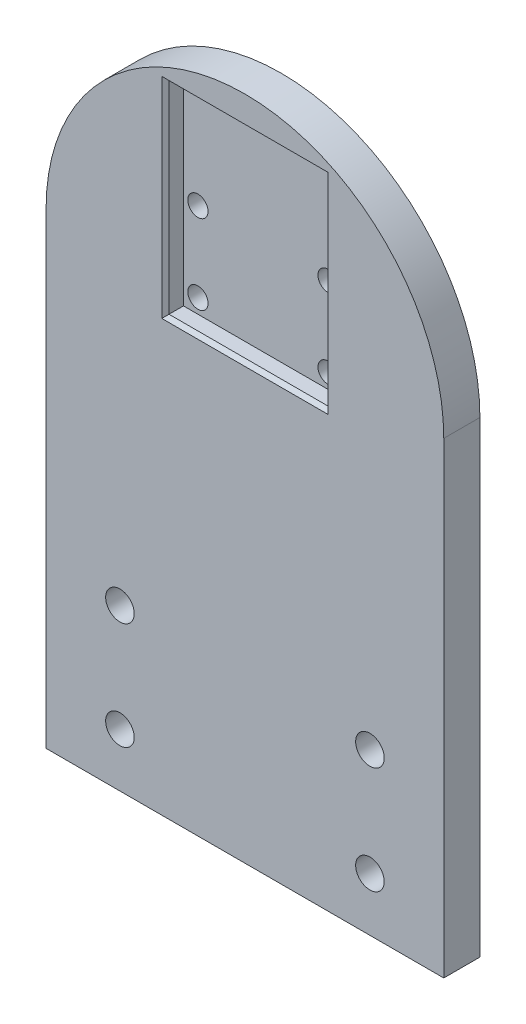
SolidWorks part; units mm, degrees
ref_plane "Front" through (0, 0, 0) normal (0, 0, 1) x (1, 0, 0)
ref_plane "Top" through (0, 0, 0) normal (0, 1, 0) x (1, 0, 0)
ref_plane "Right" through (0, 0, 0) normal (1, 0, 0) x (0, 0, -1)
sketch "草图1" plane through (0, 0, 0) normal (0, 0, 1) x (1, 0, 0)
  line L0 (0, 49.8177) -> (0, 51.7928) construction
  line L1 (-27.5, -14.8177) -> (27.5, -14.8177)
  line L2 (-27.5, -14.8177) -> (-27.5, 14.8177)
  line L3 (-27.5, 14.8177) -> (27.5, 14.8177) construction
  line L4 (27.5, -14.8177) -> (27.5, 14.8177)
  line L5 (-27.5, -14.8177) -> (27.5, 14.8177) construction
  line L6 (-27.5, 14.8177) -> (27.5, -14.8177) construction
  line L7 (-17.2873, -7.4089) -> (17.2873, -7.4089) construction
  line L8 (-17.2873, -7.4089) -> (-17.2873, 7.4089) construction
  line L9 (-17.2873, 7.4089) -> (17.2873, 7.4089) construction
  line L10 (17.2873, -7.4089) -> (17.2873, 7.4089) construction
  line L11 (-17.2873, -7.4089) -> (17.2873, 7.4089) construction
  line L12 (-17.2873, 7.4089) -> (17.2873, -7.4089) construction
  line L13 (-27.5, 14.8177) -> (-27.5, 49.8177)
  line L14 (27.5, 14.8177) -> (27.5, 49.8177)
  line L21 (-8.8906, 46.3596) -> (8.8906, 46.3596) construction
  line L22 (-8.8906, 46.3596) -> (-8.8906, 57.226) construction
  line L23 (-8.8906, 57.226) -> (8.8906, 57.226) construction
  line L24 (8.8906, 46.3596) -> (8.8906, 57.226) construction
  line L25 (-8.8906, 46.3596) -> (8.8906, 57.226) construction
  line L26 (-8.8906, 57.226) -> (8.8906, 46.3596) construction
  circle A0 centre (-17.2873, 7.4089) radius 1.9757
  circle A1 centre (17.2873, 7.4089) radius 1.9757
  circle A2 centre (17.2873, -7.4089) radius 1.9757
  circle A3 centre (-17.2873, -7.4089) radius 1.9757
  circle A4 centre (0, 49.8177) radius 12.3481 construction
  arc A5 (27.5, 49.8177) -> (-27.5, 49.8177) centre (0, 49.8177) ccw
  point P0 (0, 0)
  point P5 (0, 0)
  dimension "D1" = 35
  dimension "D2" = 27.5
  dimension "D3" = 55
extrude "凸台-拉伸1" add sketch "草图1" along normal blind 5
sketch "草图2" plane through (0, 0, 5) normal (0, 0, 1) x (1, 0, 0)
  line L0 (-27.5, -14.8177) -> (27.5, -14.8177) construction
  line L1 (0, -14.8177) -> (0, 45.1823) construction
  line L2 (0, 45.1823) -> (-11, 45.1823) construction
  line L4 (-11, 45.1823) -> (11, 45.1823)
  line L5 (-11, 45.1823) -> (-11, 73.1823)
  line L6 (-11, 73.1823) -> (11, 73.1823)
  line L7 (11, 45.1823) -> (11, 73.1823)
  line L8 (0, 73.1823) -> (0, 45.1823) construction
  line L9 (-11, 59.1823) -> (11, 59.1823) construction
  point P61 (0, 59.1823)
extrude "切除-拉伸1" cut sketch "草图2" against normal blind 2.5
chamfer "倒角1" distance 0.5 angle 45 4 edges at (11, 59.1823, 5) (0, 45.1823, 5) (-11, 59.1823, 5) (0, 73.1823, 5)
sketch "草图3" plane through (0, 0, 2.5) normal (0, 0, 1) x (1, 0, 0)
  line L0 (0, 45.1823) -> (0, 47.1823) construction
  line L1 (-11, 45.1823) -> (11, 45.1823) construction
  line L3 (-9, 58.1823) -> (9, 58.1823) construction
  line L4 (-9, 58.1823) -> (-9, 47.1823) construction
  line L5 (-9, 47.1823) -> (9, 47.1823) construction
  line L6 (9, 58.1823) -> (9, 47.1823) construction
  line L7 (0, 47.1823) -> (0, 58.1823) construction
  line L8 (-9, 52.6823) -> (9, 52.6823) construction
  circle A0 centre (-9, 58.1823) radius 1.4
  circle A1 centre (9, 58.1823) radius 1.4
  circle A2 centre (-9, 47.1823) radius 1.4
  circle A3 centre (9, 47.1823) radius 1.4
  point P65 (0, 52.6823)
  dimension "D1" = 11
  dimension "D2" = 18
  dimension "D3" = 0
  dimension "D4" = 0
extrude "切除-拉伸2" cut sketch "草图3" against normal blind 2.5
